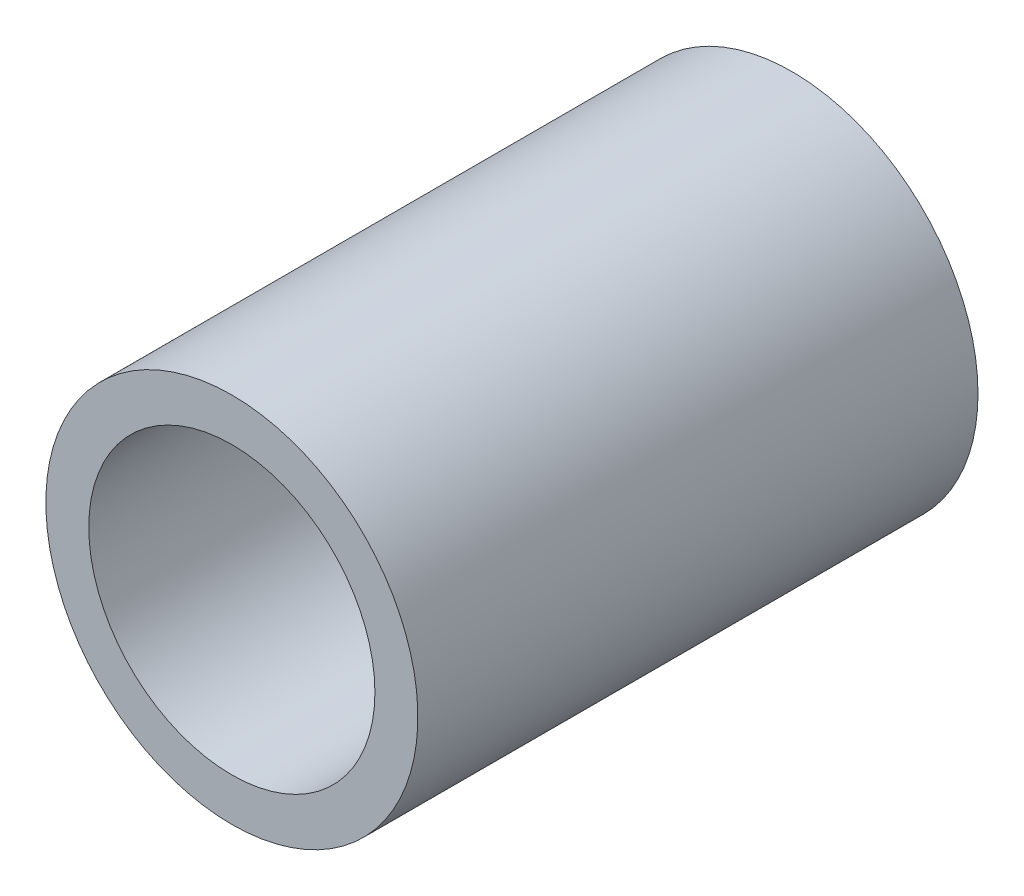
SolidWorks part; units mm, degrees
material "6061 Alloy"
ref_plane "Front Plane" through (0, 0, 0) normal (0, 0, 1) x (1, 0, 0)
ref_plane "Top Plane" through (0, 0, 0) normal (0, 1, 0) x (1, 0, 0)
ref_plane "Right Plane" through (0, 0, 0) normal (1, 0, 0) x (0, 0, -1)
sketch "Sketch1" plane through (0, 0, 0) normal (0, 0, 1) x (1, 0, 0)
  circle A0 centre (0, 0) radius 5
  circle A1 centre (0, 0) radius 6.5
  dimension "D1" = 10
  dimension "D2" = 13
extrude "Boss-Extrude1" add sketch "Sketch1" along normal up to surface (19.575 mm away)
